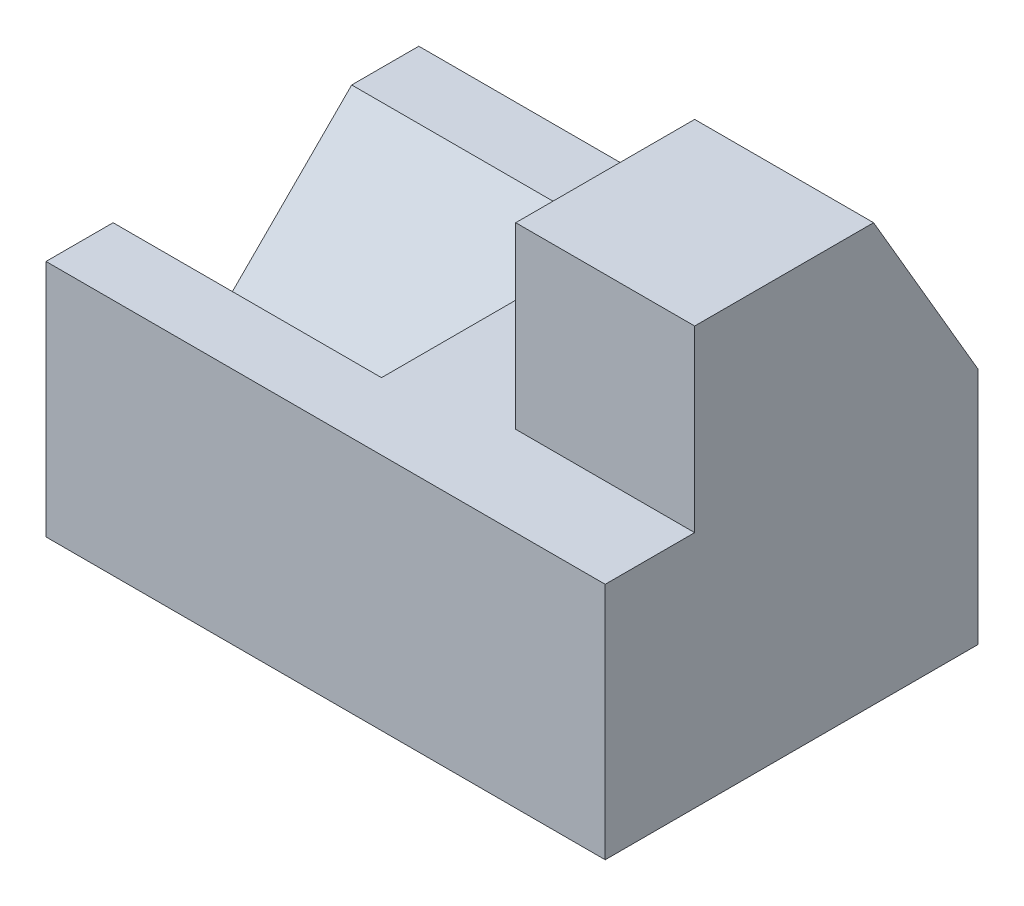
SolidWorks part; units mm, degrees
ref_plane "Front Plane" through (0, 0, 0) normal (0, 0, 1) x (1, 0, 0)
ref_plane "Top Plane" through (0, 0, 0) normal (0, 1, 0) x (1, 0, 0)
ref_plane "Right Plane" through (0, 0, 0) normal (1, 0, 0) x (0, 0, -1)
sketch "Sketch1" plane through (0, 0, 0) normal (1, 0, 0) x (0, 0, -1)
  line L0 (25, 16) -> (11, 40)
  line L1 (25, -16) -> (-25, -16)
  line L2 (25, -16) -> (25, 16)
  line L3 (25, 16) -> (-25, 16)
  line L4 (-25, -16) -> (-25, 16)
  line L5 (0, 16) -> (0, -16) construction
  line L6 (25, 0) -> (-25, 0) construction
  line L7 (11, 40) -> (-13, 40)
  line L8 (-13, 40) -> (-13, 16)
  point P0 (0, 0)
  dimension "D1" = 32
  dimension "D2" = 50
  dimension "D3" = 24
  dimension "D4" = 12
  dimension "D5" = 24
extrude "Boss-Extrude1" add sketch "Sketch1" against normal blind 75 contours L4 L1 L2 L3 region at (0, 0, 0)
extrude "Boss-Extrude2" add sketch "Sketch1<3>" against normal blind 24 contours L7 L8 L3 L0 region at (0, 27.0968, -2.7634)
sketch "Sketch1<3>" plane through (0, 0, 0) normal (1, 0, 0) x (0, 0, -1) same geometry as "Sketch1"
sketch "Sketch2" plane through (-75, 0, 0) normal (-1, 0, 0) x (0, 0, 1)
  line L0 (-16, 16) -> (0, 0)
  line L1 (-25, 16) -> (13, 16) construction
  line L2 (0, 0) -> (16, 16)
  line L3 (-25, 16) -> (25, 16) construction
  line L4 (16, 16) -> (-16, 16)
  line L6 (-25, -16) -> (-25, 16) construction
  line L7 (25, -16) -> (25, 16) construction
  point P10 (0, 0)
  dimension "D3" = 9
  dimension "D4" = 9
extrude "Cut-Extrude1" cut sketch "Sketch2" against normal blind 36
